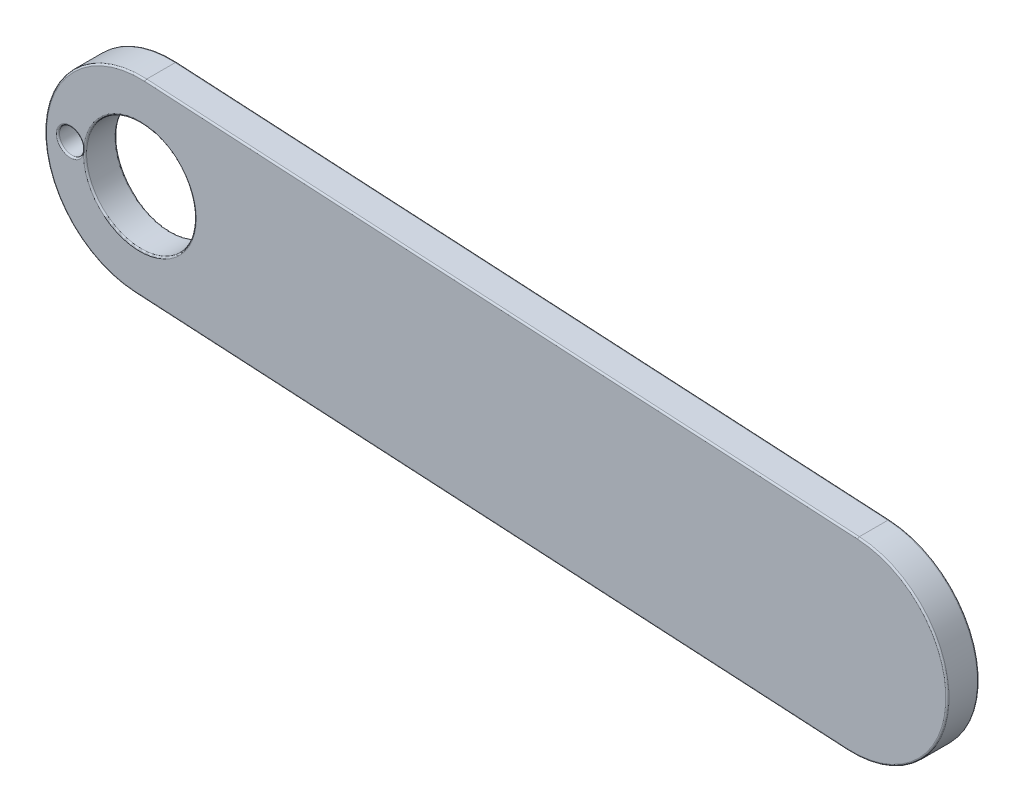
SolidWorks part; units mm, degrees
material "6061 Alloy"
ref_plane "Front Plane" through (0, 0, 0) normal (0, 0, 1) x (1, 0, 0)
ref_plane "Top Plane" through (0, 0, 0) normal (0, 1, 0) x (1, 0, 0)
ref_plane "Right Plane" through (0, 0, 0) normal (1, 0, 0) x (0, 0, -1)
sketch "Sketch1" plane through (0, 0, 0) normal (0, 0, 1) x (1, 0, 0)
  line L0 (0, 0) -> (143.002, -8.0248) construction
  line L1 (1.0673, 19.0201) -> (144.0693, 10.9952)
  line L2 (-1.0673, -19.0201) -> (141.9347, -27.0449)
  line L3 (162.0221, -9.0922) -> (-47.9177, 2.689) construction
  arc A0 (1.0673, 19.0201) -> (-1.0673, -19.0201) centre (0, 0) ccw
  arc A1 (141.9347, -27.0449) -> (144.0693, 10.9952) centre (143.002, -8.0248) ccw
  circle A2 centre (0, 0) radius 11
  circle A3 centre (-13.9481, 0.7827) radius 2.5
  point P3 (71.501, -4.0124)
  dimension "D3" = 22
  dimension "D5" = 5
  dimension "D1" = 143.002
  dimension "D2" = 38.1
  dimension "D4" = 13.97
extrude "Boss-Extrude1" add sketch "Sketch1" along normal blind 6.35
fillet "Fillet1" radius 0.3175 12 edges at (-11.4481, 0.7827, 0) (11, 0, 0) (70.4337, -23.0325, 0) (162.0221, -9.0922, 0) (72.5683, 15.0077, 0) (-19.0201, 1.0673, 0) (-11.4481, 0.7827, 6.35) (72.5683, 15.0077, 6.35) (162.0221, -9.0922, 6.35) (70.4337, -23.0325, 6.35) (-19.0201, 1.0673, 6.35) (11, 0, 6.35)
